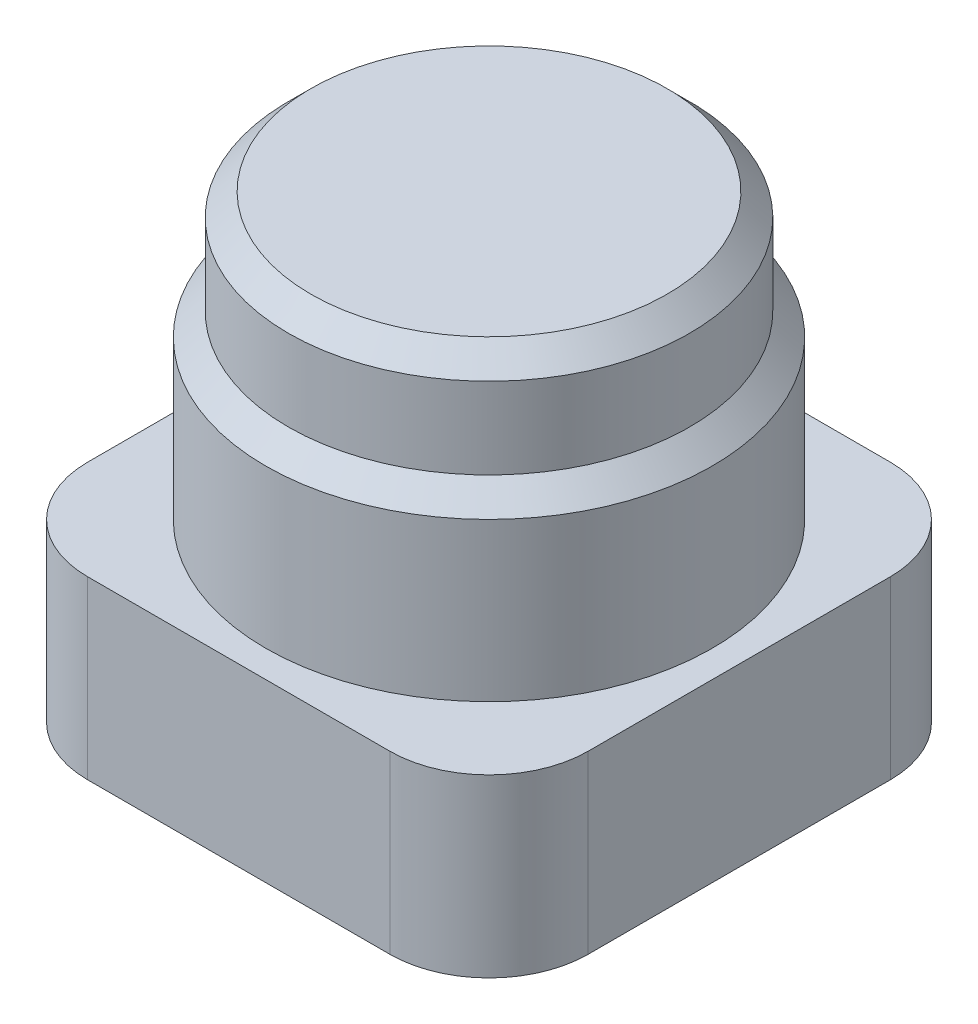
SolidWorks part; units mm, degrees
ref_plane "Front Plane" through (0, 0, 0) normal (0, 0, 1) x (1, 0, 0)
ref_plane "Top Plane" through (0, 0, 0) normal (0, 1, 0) x (1, 0, 0)
ref_plane "Right Plane" through (0, 0, 0) normal (1, 0, 0) x (0, 0, -1)
sketch "Sketch1" plane through (0, 0, 0) normal (0, 1, 0) x (1, 0, 0)
  line L1 (-16.75, -27.75) -> (16.75, -27.75)
  line L2 (-27.75, -16.75) -> (-27.75, 16.75)
  line L3 (-16.75, 27.75) -> (16.75, 27.75)
  line L4 (27.75, -16.75) -> (27.75, 16.75)
  line L5 (-27.75, -27.75) -> (27.75, 27.75) construction
  line L6 (-27.75, 27.75) -> (27.75, -27.75) construction
  arc A0 (16.75, -27.75) -> (27.75, -16.75) centre (16.75, -16.75) ccw
  arc A1 (16.75, 27.75) -> (27.75, 16.75) centre (16.75, 16.75) cw
  arc A2 (-16.75, -27.75) -> (-27.75, -16.75) centre (-16.75, -16.75) cw
  arc A3 (-27.75, 16.75) -> (-16.75, 27.75) centre (-16.75, 16.75) cw
  point P0 (0, 0)
  dimension "D3" = 11
  dimension "D1" = 55.5
  dimension "D2" = 55.5
extrude "Boss-Extrude1" add sketch "Sketch1" along normal blind 19.5
sketch "Sketch2" plane through (0, 19.5, 0) normal (0, 1, 0) x (1, 0, 0)
  circle A0 centre (0, 0) radius 24.75
  dimension "D1" = 49.5
extrude "Boss-Extrude2" add sketch "Sketch2" along normal blind 17.5
sketch "Sketch3" plane through (0, 37, 0) normal (0, 1, 0) x (1, 0, 0)
  circle A0 centre (0, 0) radius 22.25
  dimension "D1" = 44.5
extrude "Boss-Extrude3" add sketch "Sketch3" along normal blind 14
fillet "Fillet1" radius 2.5 2 edges at (0, 37, 22.25) (0, 51, 22.25) profile chamfer
sketch "Sketch4" plane through (0, 0, 0) normal (0, -1, 0) x (1, 0, 0)
  line L0 (0, 0) -> (18.013, 0) construction
  line L1 (0, 0) -> (0, -12.2307) construction
  circle A0 centre (21.5, 21.5) radius 1.25
  circle A1 centre (25, 0) radius 1.025
  circle A2 centre (21.5, -21.5) radius 1.25
  circle A3 centre (-21.5, -21.5) radius 1.25
  circle A4 centre (-25, 0) radius 1.025
  circle A5 centre (-21.5, 21.5) radius 1.25
  dimension "D1" = 21.5
  dimension "D2" = 21.5
  dimension "D3" = 2.5
  dimension "D4" = 2.05
  dimension "D5" = 25
extrude "Cut-Extrude1" cut sketch "Sketch4" against normal blind 6
